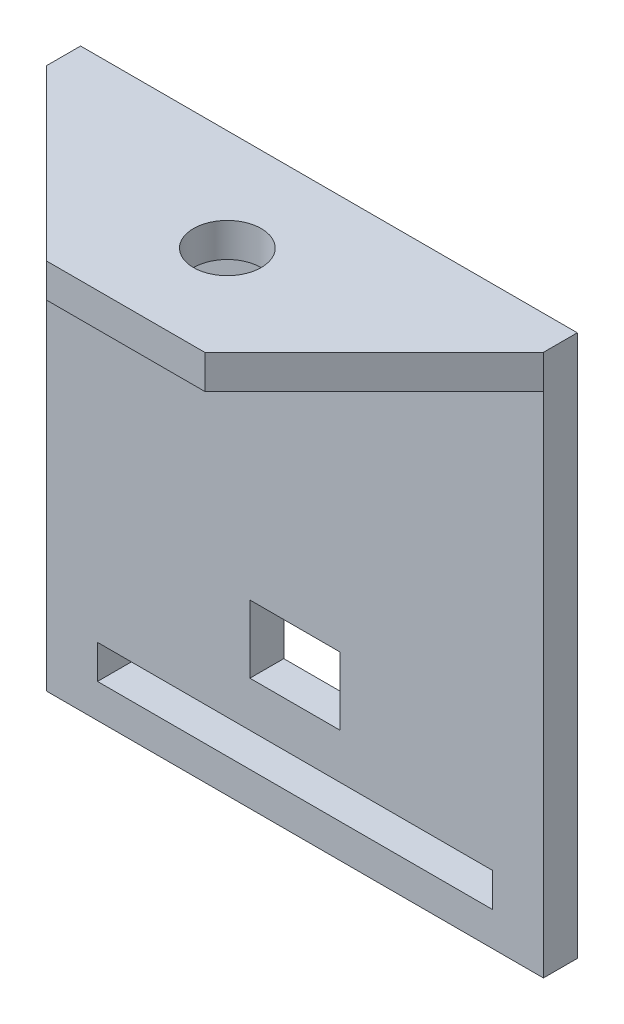
SolidWorks part; units mm, degrees
ref_plane "Piano frontale" through (0, 0, 0) normal (0, 0, 1) x (1, 0, 0)
ref_plane "Piano superiore" through (0, 0, 0) normal (0, 1, 0) x (1, 0, 0)
ref_plane "Piano destro" through (0, 0, 0) normal (1, 0, 0) x (0, 0, -1)
sketch "Schizzo8" plane through (0, 0, 0) normal (1, 0, 0) x (0, 0, -1)
  line L0 (0, 0) -> (0, 3)
  line L1 (0, 3) -> (18, 3)
  line L2 (18, 3) -> (18, -45)
  line L3 (18, -45) -> (15, -45)
  line L4 (15, -45) -> (15, 0)
  line L5 (15, 0) -> (0, 0)
  dimension "D1" = 3
  dimension "D2" = 18
  dimension "D3" = 45
  dimension "D4" = 3
extrude "Estrusione-Estrusione6" add sketch "Schizzo8" along normal blind 44
sketch "Schizzo9" plane through (0, 0, -15) normal (0, 0, 1) x (1, 0, 0)
  line L0 (44, -45) -> (0, -45) construction
  line L1 (4.5, -42) -> (39.5, -42)
  line L2 (4.5, -42) -> (4.5, -39)
  line L3 (4.5, -39) -> (39.5, -39)
  line L4 (39.5, -42) -> (39.5, -39)
  line L5 (0, 0) -> (0, -45) construction
  dimension "D1" = 3
  dimension "D2" = 35
  dimension "D3" = 3
  dimension "D4" = 4.5
extrude "Taglio-Estrusione2" cut sketch "Schizzo9" against normal blind 44
sketch "Schizzo10" plane through (0, 3, 0) normal (0, 1, 0) x (1, 0, 0)
  line L0 (0, 18) -> (44, 0) construction
  line L1 (44, 18) -> (44, 0) construction
  line L2 (44, 0) -> (44, 18) construction
  line L3 (44, 18) -> (0, 0) construction
  circle A0 centre (22, 9) radius 3
  dimension "D1" = 6
extrude "Taglio-Estrusione3" cut sketch "Schizzo10" against normal blind 10
sketch "Schizzo11" plane through (0, 0, -18) normal (0, 0, -1) x (-1, 0, 0)
  line L0 (-22, -39) -> (-22, -35) construction
  line L1 (-39.5, -39) -> (-4.5, -39) construction
  line L2 (-26, -35) -> (-18, -35)
  line L3 (-26, -35) -> (-26, -29)
  line L4 (-26, -29) -> (-18, -29)
  line L5 (-18, -29) -> (-18, -35)
  point P7 (-22, -35)
  dimension "D1" = 4
  dimension "D2" = 8
  dimension "D3" = 6
extrude "Taglio-Estrusione4" cut sketch "Schizzo11" against normal blind 10
chamfer "Smusso1" distance 15 angle 45 2 edges at (44, 1.5, 0) (0, 1.5, 0)
